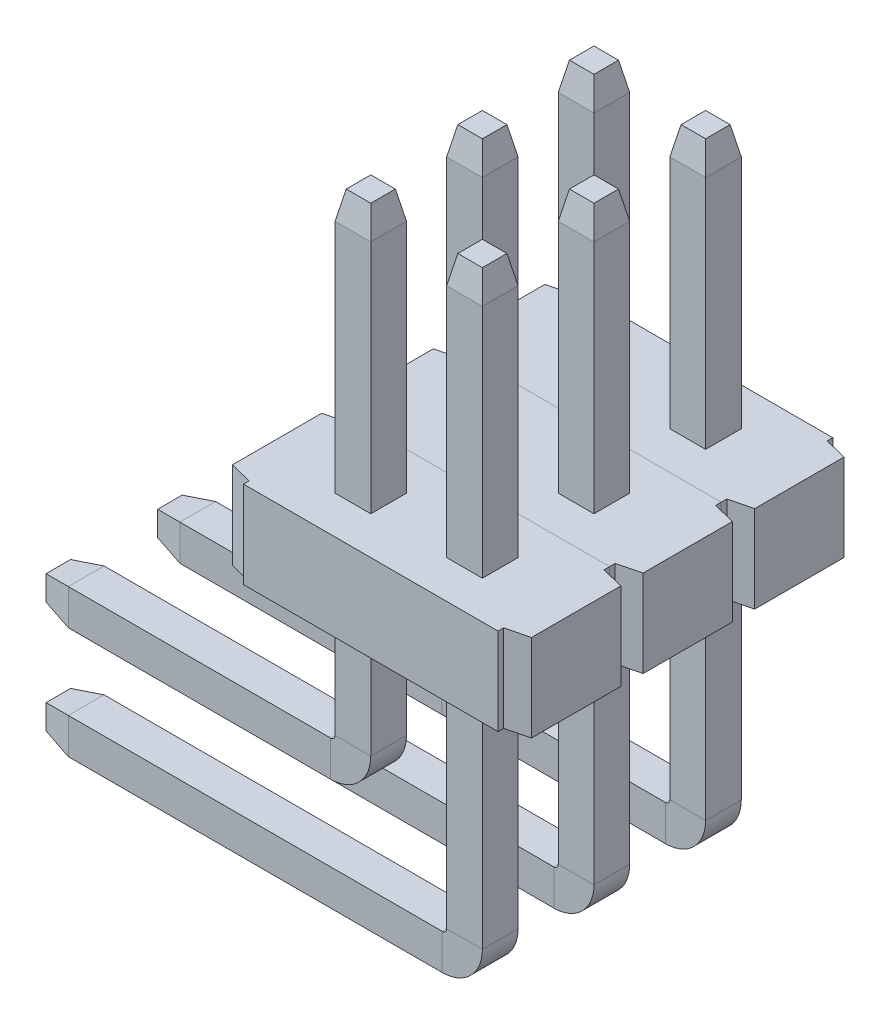
SolidWorks part; units mm, degrees
ref_plane "Front Plane" through (0, 0, 0) normal (0, 0, 1) x (1, 0, 0)
ref_plane "Top Plane" through (0, 0, 0) normal (0, 1, 0) x (1, 0, 0)
ref_plane "Right Plane" through (0, 0, 0) normal (1, 0, 0) x (0, 0, -1)
sketch "Sketch1" plane through (0, 0, 0) normal (0, 1, 0) x (1, 0, 0)
  line L0 (-1.7018, -0.508) -> (-1.4478, -0.5715)
  line L2 (-1.7018, -0.508) -> (-1.7018, 0.508)
  line L4 (1.7018, -0.508) -> (1.7018, 0.508)
  line L5 (-1.4478, 0.5715) -> (-1.4478, 0.635)
  line L6 (-1.4478, 0.635) -> (1.4478, 0.635)
  line L7 (1.4478, -0.5715) -> (1.7018, -0.508)
  line L8 (-1.7018, 0.508) -> (-1.4478, 0.5715)
  line L9 (1.4478, 0.5715) -> (1.7018, 0.508)
  line L10 (1.4478, 0.635) -> (1.4478, 0.5715)
  line L12 (-55, 0) -> (55, 0) construction
  line L13 (1.4478, -0.635) -> (1.4478, -0.5715)
  line L14 (-1.4478, -0.5715) -> (-1.4478, -0.635)
  line L15 (-1.4478, -0.635) -> (1.4478, -0.635)
  point P0 (0, 0)
  point P1 (0, -0.635)
  dimension "D1" = 1.27
  dimension "D2" = 3.4036
  dimension "D3" = 0.254
  dimension "D4" = 0.127
  dimension "D5" = 0.0635
extrude "Boss-Extrude2" add sketch "Sketch1" along normal blind 0.9906
sketch "Sketch2" plane through (0, 0, 0) normal (0, 0, 1) x (1, 0, 0)
  line L0 (-0.635, 0.9906) -> (-0.635, 3.9878)
  line L1 (0, -0.5448) -> (0, 0.5448) construction
  line L2 (0.635, 0.9906) -> (0.635, 3.9878)
  line L3 (-0.635, 0.9906) -> (-0.635, -1.397)
  line L4 (-0.889, -1.651) -> (-4.191, -1.651)
  line L5 (0.635, 0.9906) -> (0.635, -2.667)
  line L6 (0.381, -2.921) -> (-4.191, -2.921)
  line L8 (-1.4478, 0) -> (1.4478, 0) construction
  line L9 (1.4478, 0.9906) -> (-1.4478, 0.9906) construction
  arc A0 (0.635, -2.667) -> (0.381, -2.921) centre (0.381, -2.667) cw
  arc A1 (-0.635, -1.397) -> (-0.889, -1.651) centre (-0.889, -1.397) cw
  dimension "D6" = 0.254
  dimension "D1" = 1.27
  dimension "D2" = 2.9972
  dimension "D3" = 1.27
  dimension "D4" = 2.4892
  dimension "D5" = 1.651
ref_plane "Plane1" through (0, 3.9878, 0) normal (0, 1, 0) x (1, 0, 0)
sketch "Sketch3" plane through (0, 3.9878, 0) normal (0, 1, 0) x (1, 0, 0)
  line L0 (0, -0.5448) -> (0, 0.5448) construction
  line L1 (-0.8382, -0.2032) -> (-0.4318, -0.2032)
  line L2 (-0.8382, -0.2032) -> (-0.8382, 0.2032)
  line L3 (-0.8382, 0.2032) -> (-0.4318, 0.2032)
  line L4 (-0.4318, -0.2032) -> (-0.4318, 0.2032)
  line L5 (-0.8382, -0.2032) -> (-0.4318, 0.2032) construction
  line L6 (-0.8382, 0.2032) -> (-0.4318, -0.2032) construction
  line L7 (0.8382, 0.2032) -> (0.4318, -0.2032) construction
  line L8 (0.8382, -0.2032) -> (0.4318, 0.2032) construction
  line L9 (0.4318, -0.2032) -> (0.4318, 0.2032)
  line L10 (0.8382, 0.2032) -> (0.4318, 0.2032)
  line L11 (0.8382, -0.2032) -> (0.8382, 0.2032)
  line L12 (0.8382, -0.2032) -> (0.4318, -0.2032)
  point P0 (-0.635, 0)
  point P12 (0.635, 0)
  dimension "D1" = 0.4064
sketch "Sketch5" plane through (0, 3.9878, 0) normal (0, 1, 0) x (1, 0, 0)
  line L0 (-0.8382, 0.2032) -> (-0.4318, 0.2032) construction
  line L1 (-0.4318, -0.2032) -> (-0.4318, 0.2032) construction
  line L2 (-0.8382, -0.2032) -> (-0.4318, -0.2032) construction
  line L4 (-0.8382, 0.2032) -> (-0.4318, 0.2032)
  line L5 (-0.4318, -0.2032) -> (-0.4318, 0.2032)
  line L6 (-0.8382, -0.2032) -> (-0.4318, -0.2032)
  line L7 (-0.8382, -0.2032) -> (-0.8382, 0.2032)
sketch "Sketch6" plane through (0, 3.9878, 0) normal (0, 1, 0) x (1, 0, 0)
  line L0 (0.8382, 0.2032) -> (0.4318, 0.2032) construction
  line L1 (0.8382, -0.2032) -> (0.8382, 0.2032) construction
  line L2 (0.8382, -0.2032) -> (0.4318, -0.2032) construction
  line L3 (0.4318, -0.2032) -> (0.4318, 0.2032) construction
  line L4 (0.8382, 0.2032) -> (0.4318, 0.2032)
  line L5 (0.8382, -0.2032) -> (0.8382, 0.2032)
  line L6 (0.8382, -0.2032) -> (0.4318, -0.2032)
  line L7 (0.4318, -0.2032) -> (0.4318, 0.2032)
sweep "Sweep5" add profiles "Sketch5" path "Sketch2"
sketch "Sketch7" plane through (0, 0, 0) normal (0, 0, 1) x (1, 0, 0)
  line L0 (0.381, -2.921) -> (-4.191, -2.921) construction
  line L1 (0.635, 0.9906) -> (0.635, -2.667) construction
  line L2 (0.635, 0.9906) -> (0.635, 3.9878) construction
  line L3 (0.381, -2.921) -> (-4.191, -2.921)
  line L4 (0.635, 0.9906) -> (0.635, -2.667)
  line L5 (0.635, 0.9906) -> (0.635, 3.9878)
  arc A0 (0.381, -2.921) -> (0.635, -2.667) centre (0.381, -2.667) ccw construction
  arc A1 (0.381, -2.921) -> (0.635, -2.667) centre (0.381, -2.667) ccw
sweep "Sweep6" add profiles "Sketch6" path "Sketch7"
chamfer "Chamfer1" distance 0.0635 distance2 0.3175 8 edges at (-4.191, -2.921, -0.2032) (-4.191, -2.7178, 0) (-4.191, -2.921, 0.2032) (-4.191, -3.1242, 0) (-0.4318, 3.9878, 0) (-0.635, 3.9878, 0.2032) (-0.8382, 3.9878, 0) (-0.635, 3.9878, -0.2032) first distance on face at (-4.191, -2.921, 0) first distance on face at (-0.635, 3.9878, 0)
chamfer "Chamfer2" distance 0.3175 distance2 0.0635 8 edges at (0.635, 3.9878, 0.2032) (0.4318, 3.9878, 0) (0.635, 3.9878, -0.2032) (0.8382, 3.9878, 0) (-4.191, -1.4478, 0) (-4.191, -1.651, 0.2032) (-4.191, -1.8542, 0) (-4.191, -1.651, -0.2032) first distance on face at (0.635, 2.4892, 0.2032) first distance on face at (0.4318, 2.4892, 0) first distance on face at (0.635, 2.4892, -0.2032) first distance on face at (0.8382, 2.4892, 0) first distance on face at (-2.54, -1.4478, 0) first distance on face at (-2.54, -1.651, 0.2032) first distance on face at (-2.54, -1.8542, 0) first distance on face at (-2.54, -1.651, -0.2032)
pattern_linear "LPattern1" count 3 spacing 1.27 along (0, 0, -1) of bodies 105
ref_plane "Plane2" through (0, 0, -1.27) normal (0, 0, 1) x (1, 0, 0)
sketch "Sketch8" plane through (0, 3.9878, 0) normal (0, 1, 0) x (1, 0, 0)
  point P0 (-0.635, 0)
sketch "Sketch9" plane through (-4.191, 0, 0) normal (-1, 0, 0) x (0, 0, 1)
  point P0 (0, -2.921)
